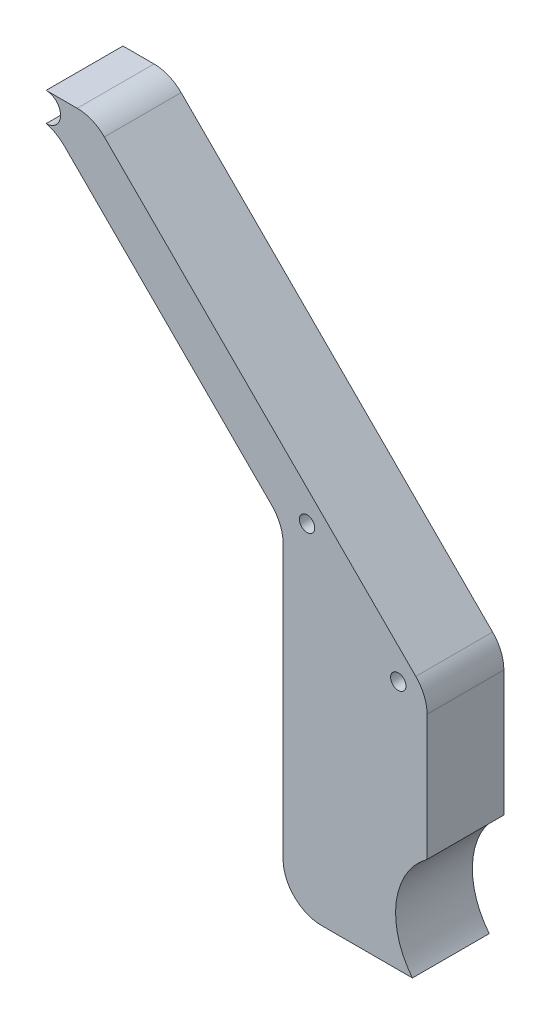
SolidWorks part; units mm, degrees
material "ABS"
ref_plane "Спереди" through (0, 0, 0) normal (0, 0, 1) x (1, 0, 0)
ref_plane "Сверху" through (0, 0, 0) normal (0, 1, 0) x (1, 0, 0)
ref_plane "Справа" through (0, 0, 0) normal (1, 0, 0) x (0, 0, -1)
sketch "Эскиз1" plane through (0, 0, 0) normal (0, 0, 1) x (1, 0, 0)
  line L0 (0.0303, 5) -> (-14.9697, 5)
  line L1 (-14.9697, 5) -> (-14.9697, 16.1412)
  line L2 (-14.9697, 16.1412) -> (-38.8284, 40)
  line L4 (-34.7574, 43) -> (0.0303, 8.2123)
  line L6 (0.0303, 8.2123) -> (0.0303, 5)
  line L8 (0.0303, 0) -> (0.0303, 61.3431) construction
  line L9 (-39.6497, 43) -> (-45.0997, 43) construction
  line L11 (-38.8284, 40) -> (-39.6497, 40)
  line L12 (-34.7574, 43) -> (-39.6497, 43)
  arc A0 (-39.6497, 43) -> (-39.6497, 40) centre (-39.6497, 41.5) cw
  arc A1 (-39.6497, 40) -> (-39.6497, 43) centre (-39.6497, 41.5) ccw construction
  dimension "D1" = 135
  dimension "D2" = 15
  dimension "D4" = 5
  dimension "D6" = 4.8923
  dimension "D7" = 35
extrude "База" add sketch "Эскиз1" against normal blind 8
hole_wizard "Крепление M2" positions "Эскиз2" profile "Эскиз3" tap size "M2" standard "DIN" end condition through all
sketch "Эскиз2" plane through (0, 0, 0) normal (0, 0, 1) x (1, 0, 0)
  line L1 (-14.9697, 5) -> (0.0303, 5) construction
  line L2 (0.0303, 5) -> (0.0303, 8.2123) construction
  point P0 (-2.9697, 8)
  point P12 (-12.4697, 17.5)
  dimension "D1" = 3
  dimension "D2" = 3
  dimension "D3" = 12.5
  dimension "D4" = 12.5
sketch "Эскиз3" plane through (-2.9697, 8, 0) normal (1, 0, 0) x (0, -1, 0)
  line L0 (0, 0) -> (0, 8)
  line L1 (0, 8) -> (0.8, 8)
  line L2 (0.8, 8) -> (0.8, 0)
  line L5 (0.8, 0) -> (0, 0)
  line L11 (0, -6.35) -> (0, 107.95) construction
  dimension "Диаметр проходного сверла" = 1.6
  dimension "Глубина проходного сверла" = 8
cosmetic thread "Отверстие резьбы1" parameters "D2"=2
cosmetic thread "Отверстие резьбы2" parameters "D2"=2
sketch "Эскиз5" plane through (0, 0, 0) normal (0, 0, 1) x (1, 0, 0)
  line L0 (0.0303, 5) -> (0.0303, 8.2123) construction
  line L1 (-14.9697, 5) -> (0.0303, 5)
  line L2 (-14.9697, 5) -> (-14.9697, -18)
  line L3 (-14.9697, -18) -> (0.0303, -18)
  line L4 (0.0303, 5) -> (0.0303, -18)
  dimension "D1" = 23
extrude "Продолжение низа" add sketch "Эскиз5" against normal up to surface (8 mm away) up to face at (-2.1697, 8, -8)
fillet "Скругление1" radius 4 5 edges at (-38.8284, 40, -4) (-14.9697, 16.1412, -4) (-34.7574, 43, -4) (0.0303, 8.2123, -4) (-14.9697, -18, -4)
sketch "Эскиз6" plane through (0, 0, 0) normal (0, 0, 1) x (1, 0, 0)
  line L3 (0.0303, -18) -> (0.0303, 6.5555) construction
  line L4 (0.0303, -6.5405) -> (0.0303, -19.4595)
  arc A3 (0.0303, -6.5405) -> (0.0303, -19.4595) centre (4.75, -13) ccw
  dimension "D2" = 4.75
  dimension "D1" = 13
  dimension "D3" = 8
extrude "Вырез-Вытянуть1" cut sketch "Эскиз6" against normal through all
